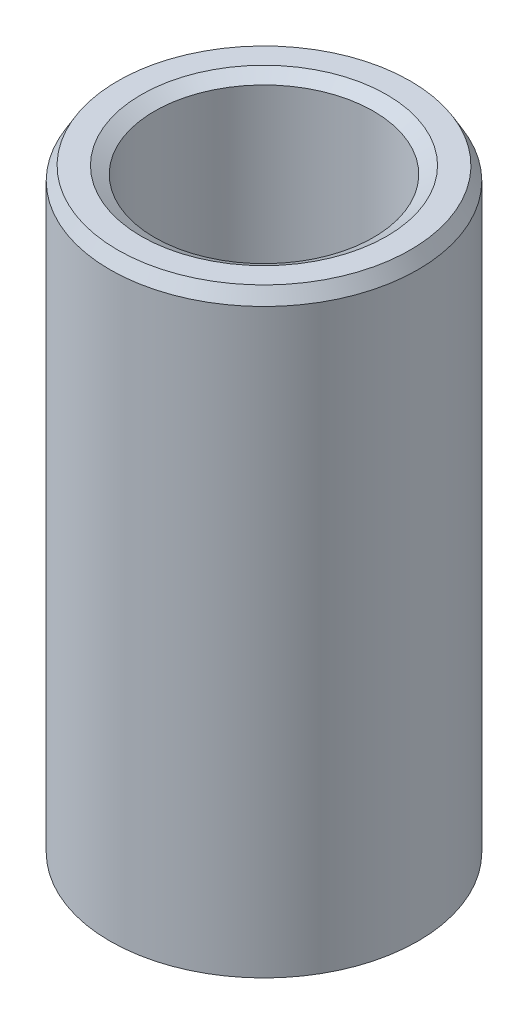
SolidWorks part; units mm, degrees
ref_plane "Front Plane" through (0, 0, 0) normal (0, 0, 1) x (1, 0, 0)
ref_plane "Top Plane" through (0, 0, 0) normal (0, 1, 0) x (1, 0, 0)
ref_plane "Right Plane" through (0, 0, 0) normal (1, 0, 0) x (0, 0, -1)
sketch "Sketch1" plane through (0, 0, 0) normal (0, 1, 0) x (1, 0, 0)
  circle A0 centre (0, 0) radius 15
  dimension "SLEEVE_OD" = 30
extrude "Boss-Extrude1" add sketch "Sketch1" along normal blind 58.6751
sketch "Sketch2" plane through (0, 0, 0) normal (0, 1, 0) x (1, 0, 0)
  circle A0 centre (0, 0) radius 10.6612
  dimension "BORE_D" = 21.3225
extrude "Cut-Extrude1" cut sketch "Sketch2" along normal through all
chamfer "Chamfer1" distance 1.2924 angle 30 4 edges at (0, 58.6751, 10.6612) (0, 0, 10.6612) (0, 0, 15) (0, 58.6751, 15) first distance on face at (0, 58.6751, 10.6612) first distance on face at (0, 0, 10.6612) first distance on face at (0, 58.6751, 15)
